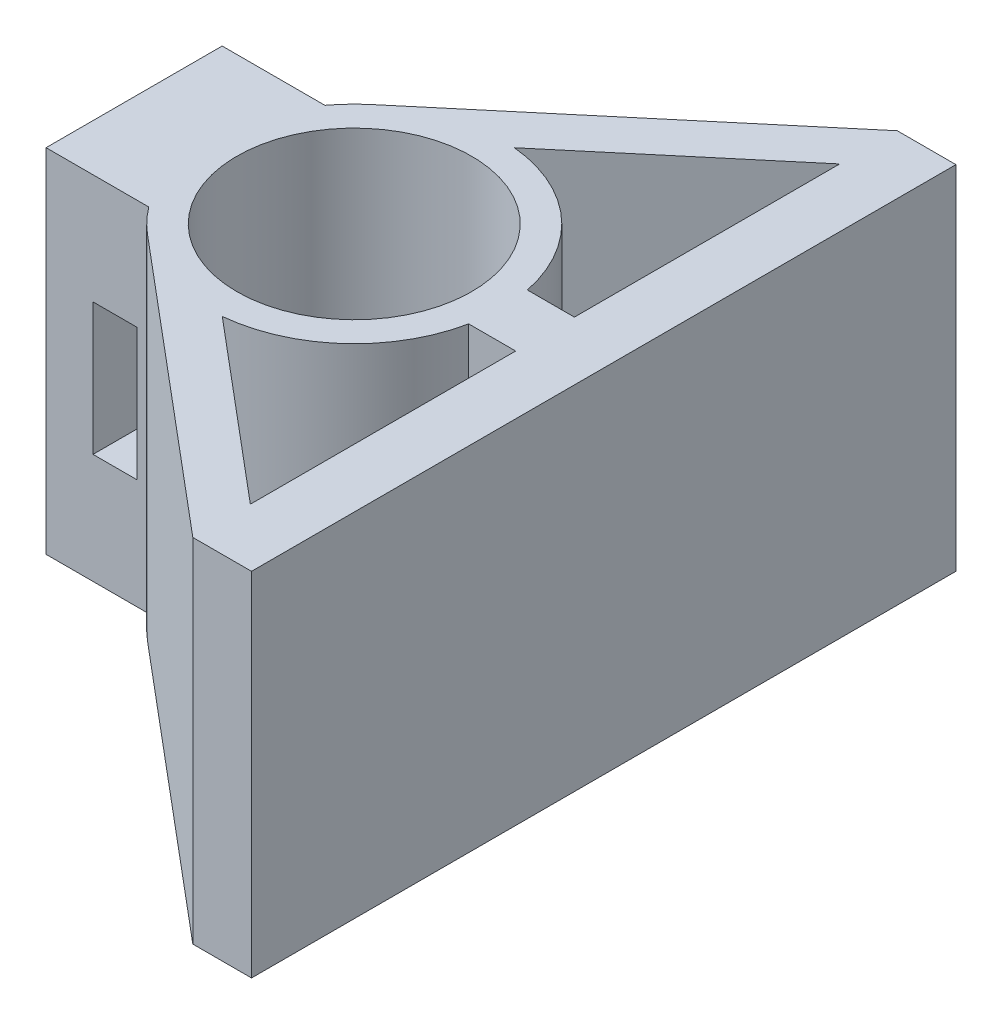
SolidWorks part; units mm, degrees
ref_plane "Front Plane" through (0, 0, 0) normal (0, 0, 1) x (1, 0, 0)
ref_plane "Top Plane" through (0, 0, 0) normal (0, 1, 0) x (1, 0, 0)
ref_plane "Right Plane" through (0, 0, 0) normal (1, 0, 0) x (0, 0, -1)
sketch "Sketch1" plane through (0, 0, 0) normal (0, 1, 0) x (1, 0, 0)
  line L0 (0, 0) -> (-14.5636, 0) construction
  line L1 (-4, 3) -> (-7.5, 3)
  line L2 (-7.5, 3) -> (-7.5, -3)
  line L3 (-4, -3) -> (-7.5, -3)
  line L4 (8.5, -1.9056) -> (8.5, 12)
  line L5 (8.5, 12) -> (6.5, 12)
  line L6 (6.5, 12) -> (-3.2183, 3.8266)
  line L7 (4.899, 1) -> (6.5, 1)
  line L8 (6.5, 1) -> (6.5, 10.04)
  line L9 (6.5, 10.04) -> (0.4799, 4.9769)
  line L10 (4.899, -1) -> (6.5, -1)
  line L11 (8.5, -1.9056) -> (8.5, -12)
  line L12 (8.5, -12) -> (6.5, -12)
  line L13 (6.5, -1) -> (6.5, -10.04)
  line L14 (6.5, -10.04) -> (0.4799, -4.9769)
  line L15 (6.5, -12) -> (-3.2183, -3.8266)
  circle A0 centre (0, 0) radius 4
  arc A1 (-4, -3) -> (-3.2183, -3.8266) centre (0, 0) ccw
  arc A2 (4.899, 1) -> (0.4799, 4.9769) centre (0, 0) ccw
  arc A3 (0.4799, -4.9769) -> (4.899, -1) centre (0, 0) ccw
  arc A4 (-3.2183, 3.8266) -> (-4, 3) centre (0, 0) ccw
  point P10 (-7.5, 0)
  point P25 (13.0223, 2.2861)
  point P26 (0, 0)
  dimension "D1" = 8
  dimension "D2" = 1
  dimension "D10" = 8.5
  dimension "D3" = 6
  dimension "D4" = 7.5
  dimension "D5" = 2
  dimension "D6" = 2
  dimension "D7" = 1.5
  dimension "D8" = 24
  dimension "D9" = 2
extrude "Boss-Extrude1" add sketch "Sketch1" along normal blind 6 and the other way blind 6
sketch "Sketch2" plane through (0, 0, -3) normal (0, 0, -1) x (-1, 0, 0)
  line L0 (-6.9549, 0) -> (16.7857, 0) construction
  line L1 (4.4, -2.25) -> (4.4, 2.25)
  line L2 (4.4, 2.25) -> (5.9, 2.25)
  line L3 (5.9, 2.25) -> (5.9, -2.25)
  line L4 (4.4, -2.25) -> (5.9, -2.25)
  point P8 (5.9, 0)
  point P9 (4.4, 0)
  dimension "D1" = 4.5
  dimension "D2" = 4.4
  dimension "D3" = 1.5
extrude "Cut-Extrude1" cut sketch "Sketch2" against normal through all
